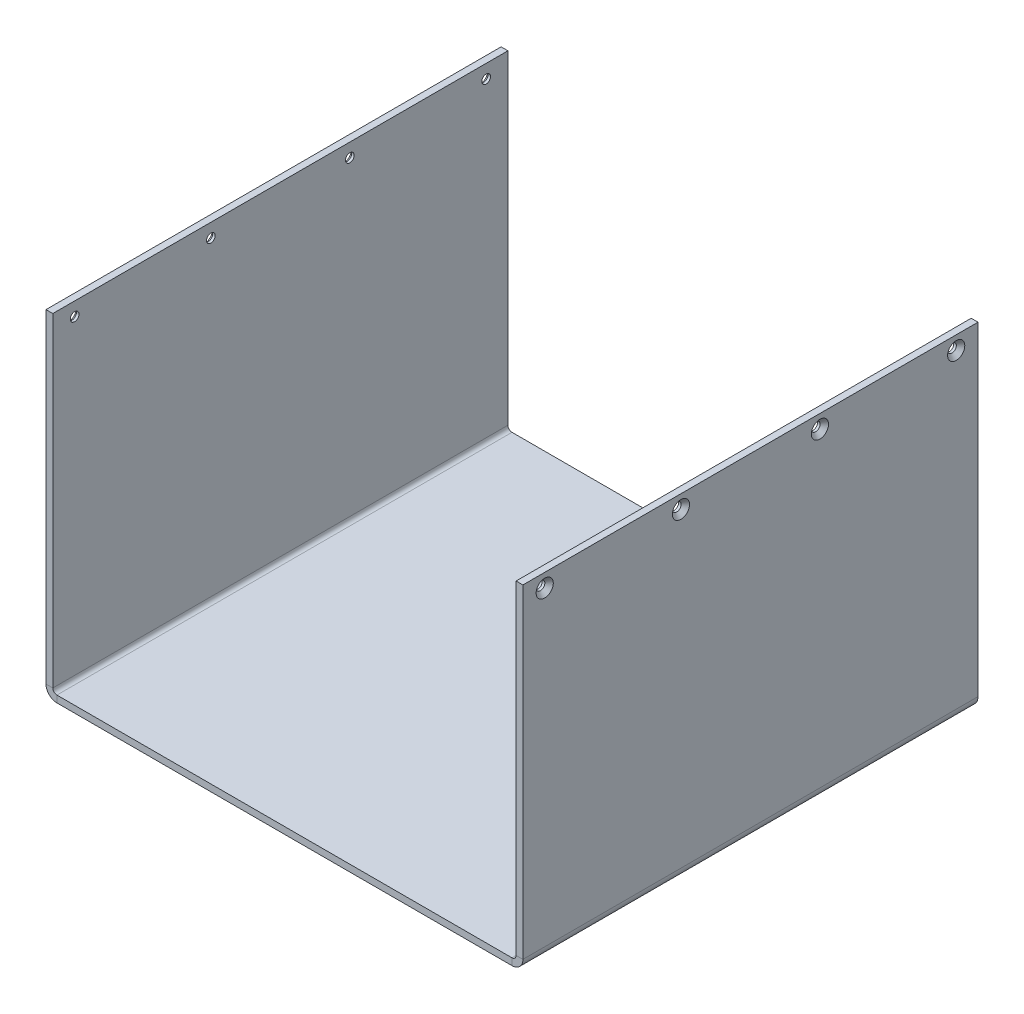
SolidWorks part; units mm, degrees
note: The reader was unsure of these and kept them because the rebuilt part matched: flange length of "Edge-Flange1", "Edge-Flange2".
material "1060 Alloy"
ref_plane "Front Plane" through (0, 0, 0) normal (0, 0, 1) x (1, 0, 0)
ref_plane "Top Plane" through (0, 0, 0) normal (0, 1, 0) x (1, 0, 0)
ref_plane "Right Plane" through (0, 0, 0) normal (1, 0, 0) x (0, 0, -1)
sketch "`" plane through (0, 0, 0) normal (0, 1, 0) x (1, 0, 0)
  line L1 (-47.7686, 30.7335) -> (122.2314, 30.7335)
  line L2 (-47.7686, 30.7335) -> (-47.7686, -136.2665)
  line L3 (-47.7686, -136.2665) -> (122.2314, -136.2665)
  line L4 (122.2314, 30.7335) -> (122.2314, -136.2665)
  line L5 (-47.7686, 30.7335) -> (122.2314, -136.2665) construction
  line L6 (-47.7686, -136.2665) -> (122.2314, 30.7335) construction
  point P4 (37.2314, -52.7665)
  dimension "D1" = 170
  dimension "D2" = 167
base flange "Base-Flange1" sketch "`" thickness 2.5 reverse thickness direction no parameters "D1"=1.5
edge flange "Edge-Flange1" sketch "Sketch8" flange angle 90 flange length 123 flange position material outside bend radius 1.5 thickness 2.5 relief rectangular parameters "D6"=10
sketch "Sketch8" plane through (-47.7686, 0, 0) normal (-1, 0, 0) x (0, 0, 1)
  line L2 (-30.7335, 0) -> (-30.7335, 120.5)
  line L3 (-30.7335, 120.5) -> (136.2665, 120.5)
  line L4 (136.2665, 120.5) -> (136.2665, 0)
  line L7 (-30.7335, 0) -> (136.2665, 0) construction
  line L8 (-30.7335, 0) -> (136.2665, 0)
bend "EdgeBend1" bend radius 1.5 bend angle 90 parameters "D5"=1
edge flange "Edge-Flange2" sketch "Sketch11" flange angle 90 flange length 123 flange position material outside bend radius 1.5 thickness 2.5 relief rectangular parameters "D6"=10
sketch "Sketch11" plane through (122.2314, 0, 0) normal (1, 0, 0) x (0, 0, -1)
  line L2 (-136.2665, 0) -> (-136.2665, 120.5)
  line L3 (-136.2665, 120.5) -> (30.7335, 120.5)
  line L4 (30.7335, 120.5) -> (30.7335, 0)
  line L7 (-136.2665, 0) -> (30.7335, 0) construction
  line L8 (-136.2665, 0) -> (30.7335, 0)
bend "EdgeBend2" bend radius 1.5 bend angle 90 parameters "D5"=2
hole_wizard "CSK for M3 Flat Head Machine Screw1" positions "Sketch12" profile "Sketch13" countersink size "M3" standard "ANSI Metric" end condition up to next
sketch "Sketch12" plane through (-50.2686, 0, 0) normal (-1, 0, 0) x (0, 0, 1)
  line L0 (136.2665, 1.5) -> (136.2665, 120.5) construction
  line L1 (-30.7335, 120.5) -> (-30.7335, 1.5) construction
  line L2 (136.2665, 120.5) -> (-30.7335, 120.5) construction
  point P0 (128.2665, 115.5)
  point P2 (78.2665, 115.5)
  point P4 (27.2665, 115.5)
  point P6 (-22.7335, 115.5)
  dimension "D1" = 8
  dimension "D2" = 8
  dimension "D3" = 50
  dimension "D4" = 50
  dimension "D5" = 5
sketch "Sketch13" plane through (-50.2686, 115.5, 128.2665) normal (0, 1, 0) x (0, 0, 1)
  line L0 (0, 0) -> (0, 2.5)
  line L1 (0, 2.5) -> (1.6, 2.5)
  line L2 (1.6, 2.5) -> (1.6, 1.55)
  line L3 (1.6, 1.55) -> (3.15, 0)
  line L5 (3.15, 0) -> (0, 0)
  line L6 (-1.6, 1.55) -> (-3.15, 0) construction
  line L11 (0, -6.35) -> (0, 107.95) construction
  dimension "Thru Hole Dia." = 3.2
  dimension "Thru Hole Depth" = 2.5
  dimension "Near C'Sink Dia." = 6.3
  dimension "Near C'Sink Angle" = 90
hole_wizard "CSK for M3 Flat Head Machine Screw2" positions "Sketch14" profile "Sketch15" countersink size "M3" standard "ANSI Metric" end condition up to next
sketch "Sketch14" plane through (124.7314, 0, 0) normal (1, 0, 0) x (0, 0, -1)
  line L0 (30.7335, 1.5) -> (30.7335, 120.5) construction
  line L1 (-136.2665, 120.5) -> (-136.2665, 1.5) construction
  line L2 (30.7335, 120.5) -> (-136.2665, 120.5) construction
  point P0 (22.7335, 115.5)
  point P2 (-27.2665, 115.5)
  point P4 (-78.2665, 115.5)
  point P6 (-128.2665, 115.5)
  dimension "D1" = 8
  dimension "D2" = 50
  dimension "D3" = 50
  dimension "D4" = 8
  dimension "D5" = 5
sketch "Sketch15" plane through (124.7314, 115.5, -22.7335) normal (0, 1, 0) x (0, 0, -1)
  line L0 (0, 0) -> (0, 2.5)
  line L1 (0, 2.5) -> (1.6, 2.5)
  line L2 (1.6, 2.5) -> (1.6, 1.55)
  line L3 (1.6, 1.55) -> (3.15, 0)
  line L5 (3.15, 0) -> (0, 0)
  line L6 (-1.6, 1.55) -> (-3.15, 0) construction
  line L11 (0, -6.35) -> (0, 107.95) construction
  dimension "Thru Hole Dia." = 3.2
  dimension "Thru Hole Depth" = 2.5
  dimension "Near C'Sink Dia." = 6.3
  dimension "Near C'Sink Angle" = 90
sketch "Bend-Lines1" [suppressed] plane through (0, 0, 0) normal (0, 1, 0) x (1, 0, 0)
sketch "Bounding-Box1" [suppressed] plane through (0, 0, 0) normal (0, 1, 0) x (1, 0, 0)
sheet metal parameters "Sheet-Metal1" thickness 2.5 parameters "D1"=1.5
flat pattern "Flat-Pattern1" [suppressed]
sketch "Bend-Lines2" plane through (0, 0, 0) normal (0, 1, 0) x (1, 0, 0)
sketch3d "Bounding-Box2" [suppressed]
  line L0 (-122.2314, -136.2665, 0) -> (47.7686, -136.2665, 0) construction
  line L1 (-122.2314, 30.7335, 0) -> (47.7686, 30.7335, 0) construction
  line L2 (-122.2314, -136.2665, 0) -> (-122.2314, 30.7335, 0) construction
  line L3 (47.7686, -136.2665, 0) -> (47.7686, 30.7335, 0) construction
sheet metal parameters "Sheet-Metal2" thickness 2.5 parameters "D1"=1.5
flat pattern "Flat-Pattern1"
sketch "Bend-Lines2" plane through (0, 0, 0) normal (0, 1, 0) x (1, 0, 0)
  line L0 (-45.9284, 30.7335) -> (-45.9284, -136.2665) construction
  line L1 (-45.9284, 30.7335) -> (-45.9284, -136.2665) construction
sketch3d "Bounding-Box2" [suppressed]
  line L0 (122.2314, -136.2665, 0) -> (-97.0883, -136.2665, 0) construction
  line L1 (122.2314, 30.7335, 0) -> (-97.0883, 30.7335, 0) construction
  line L2 (122.2314, -136.2665, 0) -> (122.2314, 30.7335, 0) construction
  line L3 (-97.0883, -136.2665, 0) -> (-97.0883, 30.7335, 0) construction
bend of the flat pattern "Flatten-<EdgeBend1>1"
sheet metal parameters "Sheet-Metal3" thickness 2.5 parameters "D1"=1.5
flat pattern "Flat-Pattern1"
sketch "Bend-Lines2" plane through (0, 0, 0) normal (0, 1, 0) x (1, 0, 0)
  line L0 (-48.4284, 30.7335) -> (-48.4284, -136.2665) construction
  line L1 (-48.4284, 30.7335) -> (-48.4284, -136.2665) construction
  line L2 (122.8912, -136.2665) -> (122.8912, 30.7335) construction
  line L3 (122.8912, -136.2665) -> (122.8912, 30.7335) construction
sketch3d "Bounding-Box2" [suppressed]
  line L0 (244.0511, -136.2665, 0) -> (-169.5883, -136.2665, 0) construction
  line L1 (244.0511, 30.7335, 0) -> (-169.5883, 30.7335, 0) construction
  line L2 (244.0511, -136.2665, 0) -> (244.0511, 30.7335, 0) construction
  line L3 (-169.5883, -136.2665, 0) -> (-169.5883, 30.7335, 0) construction
bend of the flat pattern "Flatten-<EdgeBend1>1"
bend of the flat pattern "Flatten-<EdgeBend2>1"
sheet metal parameters "Sheet-Metal4" thickness 2.5 parameters "D1"=1.5
flat pattern "Flat-Pattern1"
sketch "Bend-Lines2" plane through (0, 0, 0) normal (0, 1, 0) x (1, 0, 0)
  line L0 (-48.4284, 30.7335) -> (-48.4284, -136.2665) construction
  line L1 (-48.4284, 30.7335) -> (-48.4284, -136.2665) construction
  line L2 (122.8912, -136.2665) -> (122.8912, 30.7335) construction
  line L3 (122.8912, -136.2665) -> (122.8912, 30.7335) construction
sketch3d "Bounding-Box2" [suppressed]
  line L0 (244.0511, -136.2665, 0) -> (-169.5883, -136.2665, 0) construction
  line L1 (244.0511, 30.7335, 0) -> (-169.5883, 30.7335, 0) construction
  line L2 (244.0511, -136.2665, 0) -> (244.0511, 30.7335, 0) construction
  line L3 (-169.5883, -136.2665, 0) -> (-169.5883, 30.7335, 0) construction
bend of the flat pattern "Flatten-<EdgeBend1>1"
bend of the flat pattern "Flatten-<EdgeBend2>1"
sheet metal parameters "Sheet-Metal5" thickness 2.5 parameters "D1"=1.5
flat pattern "Flat-Pattern1"
sketch "Bend-Lines2" plane through (0, 0, 0) normal (0, 1, 0) x (1, 0, 0)
  line L0 (-48.4284, 30.7335) -> (-48.4284, -136.2665) construction
  line L1 (-48.4284, 30.7335) -> (-48.4284, -136.2665) construction
  line L2 (122.8912, -136.2665) -> (122.8912, 30.7335) construction
  line L3 (122.8912, -136.2665) -> (122.8912, 30.7335) construction
sketch3d "Bounding-Box2" [suppressed]
  line L0 (244.0511, -136.2665, 0) -> (-169.5883, -136.2665, 0) construction
  line L1 (244.0511, 30.7335, 0) -> (-169.5883, 30.7335, 0) construction
  line L2 (244.0511, -136.2665, 0) -> (244.0511, 30.7335, 0) construction
  line L3 (-169.5883, -136.2665, 0) -> (-169.5883, 30.7335, 0) construction
bend of the flat pattern "Flatten-<EdgeBend1>1"
bend of the flat pattern "Flatten-<EdgeBend2>1"
